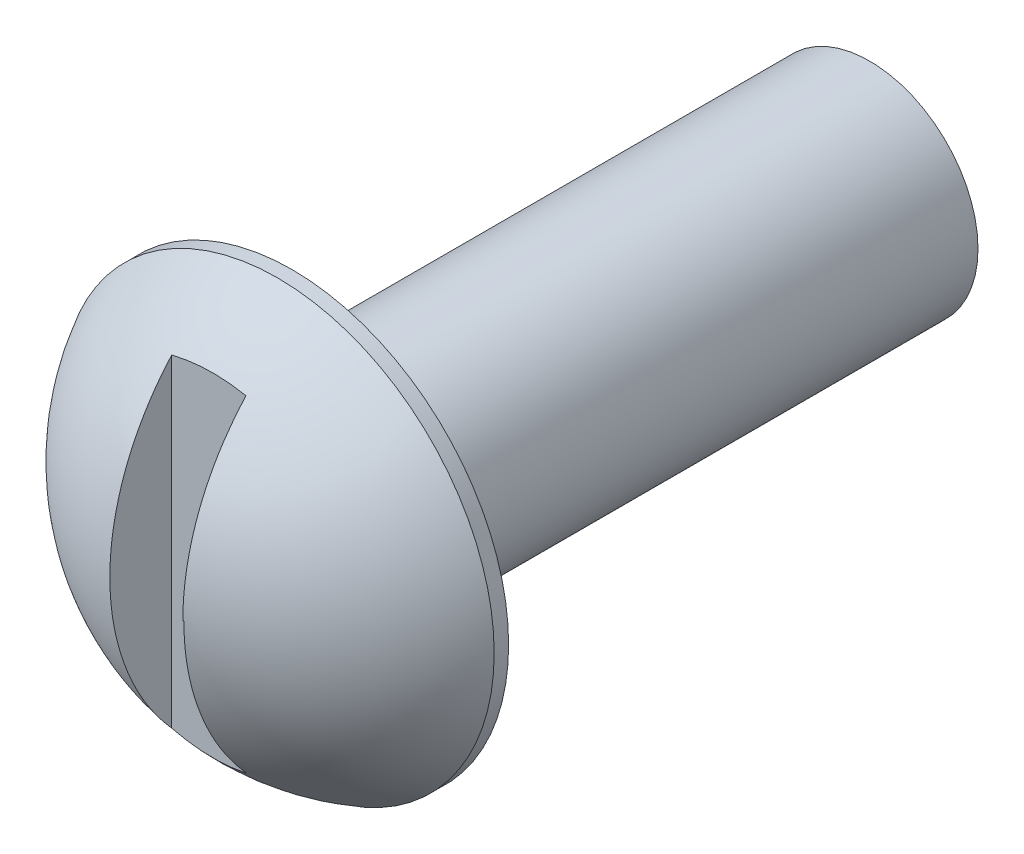
SolidWorks part; units mm, degrees
ref_plane "Спереди" through (0, 0, 0) normal (0, 0, 1) x (1, 0, 0)
ref_plane "Сверху" through (0, 0, 0) normal (0, 1, 0) x (1, 0, 0)
ref_plane "Справа" through (0, 0, 0) normal (1, 0, 0) x (0, 0, -1)
sketch "Эскиз1" plane through (0, 0, 0) normal (0, 0, 1) x (1, 0, 0)
  circle A0 centre (0, 0) radius 1.5
  dimension "D1" = 3
extrude "Вытянуть1" add sketch "Эскиз1" along normal blind 8
sketch "Эскиз2" plane through (0, 0, 8) normal (0, 0, 1) x (1, 0, 0)
  circle A0 centre (0, 0) radius 3
  dimension "D1" = 6
extrude "Вытянуть2" add sketch "Эскиз2" along normal blind 0.2
dome "Купол1" faces to dome 1 distance 1.8 reverse direction no elliptical dome no face at (3, 0, 8.2) parameters "D1"=1.8
sketch "Эскиз4" plane through (0, 0, 0) normal (0, 1, 0) x (1, 0, 0)
  line L0 (0, -12.0275) -> (0, -7.2711) construction
  line L1 (0, -8) -> (0, 0) construction
  line L2 (-0.5698, -11.3999) -> (-0.5698, -9.096)
  line L3 (0.4707, -11.3999) -> (0.4707, -9.096)
  line L4 (-0.5698, -9.096) -> (0.4707, -9.096)
  line L5 (-0.5698, -11.3999) -> (0.4707, -11.3999)
  point P4 (0, -9.6493)
  point P5 (-0.5698, -9.096)
  point P6 (0.4707, -9.096)
extrude "Вырез-Вытянуть3" cut sketch "Эскиз4" against normal blind 50
sketch "Эскиз7" plane through (0, 0, 0) normal (0, -1, 0) x (1, 0, 0)
  line L1 (-0.5698, 9.096) -> (0.4576, 9.096)
  line L2 (-0.5698, 9.096) -> (-0.5698, 10.8993)
  line L3 (-0.5698, 10.8993) -> (0.4576, 10.8993)
  line L4 (0.4576, 9.096) -> (0.4576, 10.8993)
  dimension "D1" = 1.0274
  dimension "D2" = 1.8033
extrude "Вырез-Вытянуть6" cut sketch "Эскиз7" against normal blind 50
